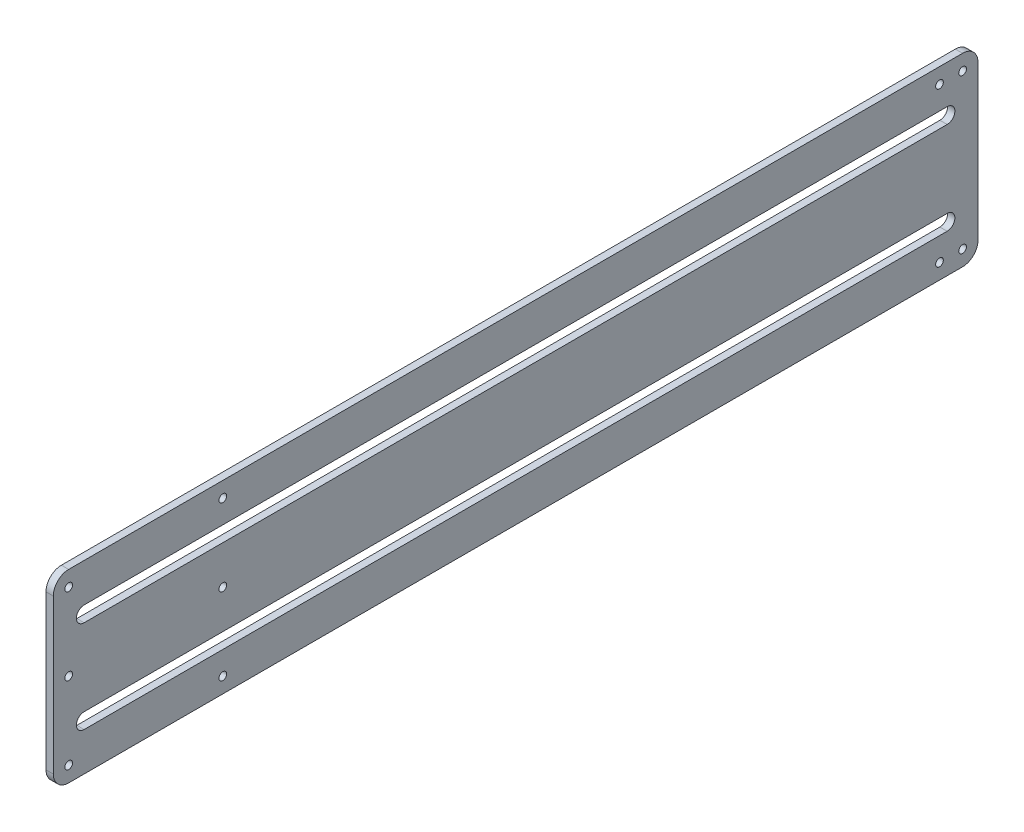
SolidWorks part; units mm, degrees
ref_plane "Front Plane" through (0, 0, 0) normal (0, 0, 1) x (1, 0, 0)
ref_plane "Top Plane" through (0, 0, 0) normal (0, 1, 0) x (1, 0, 0)
ref_plane "Right Plane" through (0, 0, 0) normal (1, 0, 0) x (0, 0, -1)
sketch "Sketch1" plane through (0, 0, 0) normal (1, 0, 0) x (0, 0, -1)
  line L1 (-184.15, -38.1) -> (184.15, -38.1)
  line L2 (-190.5, -31.75) -> (-190.5, 31.75)
  line L3 (-184.15, 38.1) -> (184.15, 38.1)
  line L4 (190.5, -31.75) -> (190.5, 31.75)
  line L5 (-190.5, -38.1) -> (190.5, 38.1) construction
  line L6 (-190.5, 38.1) -> (190.5, -38.1) construction
  arc A0 (-190.5, -31.75) -> (-184.15, -38.1) centre (-184.15, -31.75) ccw
  arc A1 (184.15, -38.1) -> (190.5, -31.75) centre (184.15, -31.75) ccw
  arc A2 (190.5, 31.75) -> (184.15, 38.1) centre (184.15, 31.75) ccw
  arc A3 (-184.15, 38.1) -> (-190.5, 31.75) centre (-184.15, 31.75) ccw
  point P0 (0, 0)
  dimension "D3" = 6.35
  dimension "D1" = 381
  dimension "D2" = 76.2
extrude "Outer Cut" add sketch "Sketch1" along normal mid plane 2.9972
sketch "Sketch2" plane through (1.4986, 0, 0) normal (1, 0, 0) x (0, 0, -1)
  line L0 (-177.8, 19.05) -> (177.8, 19.05) construction
  line L1 (-177.8, 22.225) -> (177.8, 22.225)
  line L2 (-177.8, 15.875) -> (177.8, 15.875)
  line L3 (-190.5, 0) -> (190.5, 0) construction
  line L6 (190.5, -31.75) -> (190.5, 31.75) construction
  line L7 (-190.5, 31.75) -> (-190.5, -31.75) construction
  line L8 (-177.8, -19.05) -> (177.8, -19.05) construction
  line L9 (-177.8, -22.225) -> (177.8, -22.225)
  line L10 (-177.8, -15.875) -> (177.8, -15.875)
  arc A0 (-177.8, 22.225) -> (-177.8, 15.875) centre (-177.8, 19.05) ccw
  arc A1 (177.8, 15.875) -> (177.8, 22.225) centre (177.8, 19.05) ccw
  arc A2 (-177.8, -22.225) -> (-177.8, -15.875) centre (-177.8, -19.05) cw
  arc A3 (177.8, -15.875) -> (177.8, -22.225) centre (177.8, -19.05) cw
  point P2 (0, 19.05)
  point P18 (0, -19.05)
  dimension "D1" = 6.35
  dimension "D2" = 38.1
  dimension "D3" = 12.7
  dimension "D4" = 12.7
extrude "Slots" cut sketch "Sketch2" against normal through all
sketch "Sketch3" plane through (1.4986, 0, 0) normal (1, 0, 0) x (0, 0, -1)
  line L0 (-184.15, 31.75) -> (-120.65, 31.75) construction
  line L1 (184.15, 38.1) -> (-184.15, 38.1) construction
  line L2 (-190.5, 31.75) -> (-190.5, -31.75) construction
  line L3 (0, 0) -> (-190.5, 0) construction
  circle A0 centre (-184.15, 31.75) radius 1.5875
  circle A1 centre (-120.65, 31.75) radius 1.5875
  circle A2 centre (-120.65, -31.75) radius 1.5875
  circle A3 centre (-184.15, -31.75) radius 1.5875
  circle A4 centre (-184.15, 0) radius 1.5875
  circle A5 centre (-120.65, 0) radius 1.5875
  dimension "D1" = 3.175
  dimension "D3" = 63.5
  dimension "D4" = 6.35
  dimension "D5" = 6.35
extrude "Mount Holes" cut sketch "Sketch3" against normal through all
sketch "Sketch4" plane through (1.4986, 0, 0) normal (1, 0, 0) x (0, 0, -1)
  line L0 (190.5, -31.75) -> (190.5, 31.75) construction
  line L1 (184.15, 38.1) -> (-184.15, 38.1) construction
  line L2 (0, 0) -> (190.5, 0) construction
  circle A0 centre (184.15, 31.75) radius 1.5875
  circle A2 centre (174.625, 31.75) radius 1.5875
  circle A3 centre (174.625, -31.75) radius 1.5875
  circle A4 centre (184.15, -31.75) radius 1.5875
  dimension "D3" = 3.175
  dimension "D1" = 6.35
  dimension "D2" = 6.35
  dimension "D5" = 9.525
  dimension "D4" = 2
extrude "Cut-Extrude1" cut sketch "Sketch4" against normal through all
